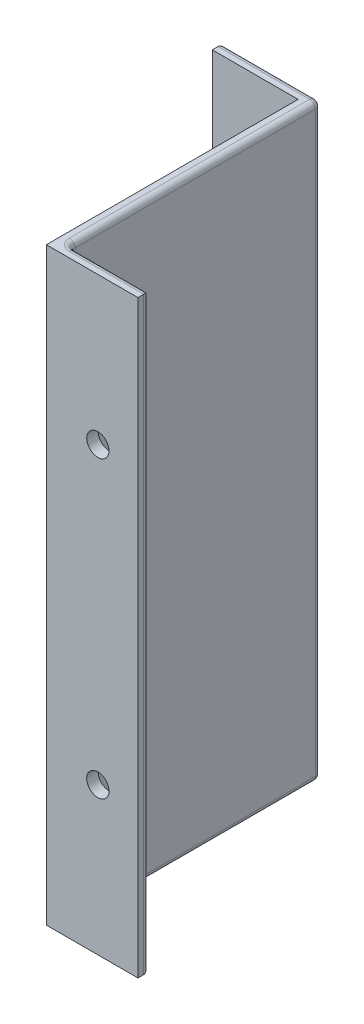
SolidWorks part; units mm, degrees
ref_plane "Plano frontal" through (0, 0, 0) normal (0, 0, 1) x (1, 0, 0)
ref_plane "Plano superior" through (0, 0, 0) normal (0, 1, 0) x (1, 0, 0)
ref_plane "Plano direito" through (0, 0, 0) normal (1, 0, 0) x (0, 0, -1)
sketch "Esboço1" plane through (0, 0, 0) normal (0, 1, 0) x (1, 0, 0)
  line L0 (0, 0) -> (16, 0)
  line L1 (16, 0) -> (16, 2)
  line L2 (16, 2) -> (2, 2)
  line L3 (2, 2) -> (2, 46)
  line L4 (2, 46) -> (-15, 46)
  line L5 (-15, 46) -> (-15, 44)
  line L6 (-15, 44) -> (0, 44)
  line L7 (0, 44) -> (0, 0)
  dimension "D1" = 16
  dimension "D2" = 2
  dimension "D3" = 2
  dimension "D4" = 2
  dimension "D5" = 44
  dimension "D6" = 17
extrude "Ressalto-extrusão1" add sketch "Esboço1" along normal blind 103
sketch "Esboço2" plane through (0, 0, -2) normal (0, 0, -1) x (-1, 0, 0)
  line L0 (-16, 0) -> (-2, 0) construction
  line L1 (-16, 103) -> (-2, 103) construction
  line L2 (-16, 0) -> (-2, 0) construction
  line L3 (-16, 103) -> (-2, 103) construction
  line L4 (-9, 103) -> (-9, 51.5) construction
  line L5 (-9, 51.5) -> (-16, 51.5) construction
  line L6 (-16, 103) -> (-16, 0) construction
  circle A0 centre (-9, 77.25) radius 1.95
  circle A1 centre (-9, 25.75) radius 1.95
  dimension "D1" = 3.9
extrude "Corte-extrusão1" cut sketch "Esboço2" against normal blind 2
sketch "Esboço3" plane through (0, 0, -2) normal (0, 0, -1) x (-1, 0, 0)
  line L0 (-9, 77.25) -> (-9, 25.75) construction
  text T0 "FONTE 12V"
extrude "Corte-extrusão2" cut sketch "Esboço3" against normal blind 0.5
fillet "Filete1" radius 1 10 edges at (9, 103, -2) (9, 0, -2) (2, 51.5, -2) (2, 103, -24) (2, 0, -24) (-6.5, 103, -46) (-15, 51.5, -46) (-6.5, 0, -46) (16, 51.5, -2) (2, 51.5, -46)
equation "\"D3@Esboço1\"=\"D2@Esboço1\""
equation "\"D4@Esboço1\"=\"D2@Esboço1\""
